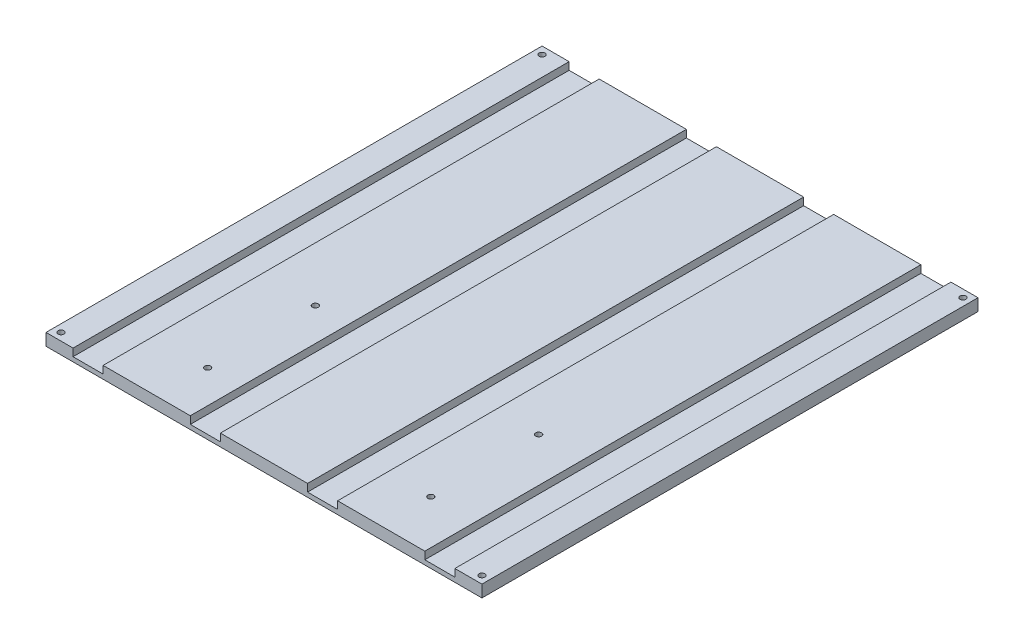
SolidWorks part; units mm, degrees
ref_plane "Front Plane" through (0, 0, 0) normal (0, 0, 1) x (1, 0, 0)
ref_plane "Top Plane" through (0, 0, 0) normal (0, 1, 0) x (1, 0, 0)
ref_plane "Right Plane" through (0, 0, 0) normal (1, 0, 0) x (0, 0, -1)
sketch "Sketch2" plane through (0, 0, 0) normal (0, 1, 0) x (1, 0, 0)
  line L0 (-24.5, -82.5) -> (-24.5, 82.5)
  line L1 (-72.5, -82.5) -> (72.5, -82.5)
  line L2 (-72.5, -82.5) -> (-72.5, 82.5)
  line L3 (-72.5, 82.5) -> (72.5, 82.5)
  line L4 (72.5, -82.5) -> (72.5, 82.5)
  line L5 (-63.5, -82.5) -> (-53.5, -82.5)
  line L6 (-63.5, -82.5) -> (-63.5, 82.5)
  line L7 (-63.5, 82.5) -> (-53.5, 82.5)
  line L8 (-53.5, -82.5) -> (-53.5, 82.5)
  line L9 (-63.5, -82.5) -> (-53.5, 82.5) construction
  line L10 (-63.5, 82.5) -> (-53.5, -82.5) construction
  line L11 (-24.5, -82.5) -> (-14.5, -82.5)
  line L12 (-14.5, -82.5) -> (-14.5, 82.5)
  line L13 (-24.5, 82.5) -> (-14.5, 82.5)
  line L14 (14.5, -82.5) -> (14.5, 82.5)
  line L15 (14.5, -82.5) -> (24.5, -82.5)
  line L16 (24.5, -82.5) -> (24.5, 82.5)
  line L17 (14.5, 82.5) -> (24.5, 82.5)
  line L18 (53.5, -82.5) -> (53.5, 82.5)
  line L19 (53.5, -82.5) -> (63.5, -82.5)
  line L20 (63.5, -82.5) -> (63.5, 82.5)
  line L21 (53.5, 82.5) -> (63.5, 82.5)
  point P0 (0, 0)
  point P6 (0, 82.5)
  point P7 (-72.5, 0)
  point P8 (-58.5, 0)
  dimension "D1" = 145
  dimension "D2" = 165
  dimension "D3" = 10
  dimension "D4" = 165
  dimension "D5" = 58.5
  dimension "D6" = 4
  dimension "D7" = 29
extrude "Boss-Extrude1" add sketch "Sketch2" against normal blind 4 contours L2 L1 L4 L3
extrude "Cut-Extrude1" cut sketch "Sketch2<3>" against normal blind 2.5 contours L6 L5 L8 L7 | L0 L13 L12 L11 | L14 L17 L16 L15 | L18 L21 L20 L19
sketch "Sketch2<3>" plane through (0, 0, 0) normal (0, 1, 0) x (1, 0, 0) same geometry as "Sketch2"
sketch "Sketch3" plane through (0, -4, 0) normal (0, -1, 0) x (1, 0, 0)
  line L0 (-70, -80) -> (70, 80)
  line L1 (-70, 80) -> (70, 80) construction
  line L2 (-70, 80) -> (-70, -80) construction
  line L3 (-70, -80) -> (70, -80) construction
  line L4 (70, 80) -> (70, -80) construction
  circle A0 centre (-70, 80) radius 0.98
  circle A1 centre (-70, 80) radius 2
  circle A2 centre (70, 80) radius 2
  circle A3 centre (70, 80) radius 0.98
  circle A4 centre (70, -80) radius 2
  circle A5 centre (70, -80) radius 0.98
  circle A6 centre (-70, -80) radius 2
  circle A7 centre (-70, -80) radius 0.98
  point P11 (0, 0)
  dimension "D1" = 1.96
  dimension "D2" = 4
  dimension "D3" = 160
  dimension "D4" = 140
extrude "Cut-Extrude3" cut sketch "Sketch3" against normal blind 5 contours A5 | A7 | A0 | A3
sketch "Sketch5" plane through (0, -4, 0) normal (0, 1, 0) x (1, 0, 0)
  line L1 (-35.4387, -29.9718) -> (38.8313, -29.9718) construction
  line L2 (-35.4387, -29.9718) -> (-35.4387, -65.8118) construction
  line L3 (-35.4387, -65.8118) -> (38.8313, -65.8118) construction
  line L4 (38.8313, -29.9718) -> (38.8313, -65.8118) construction
  circle A0 centre (-35.4387, -29.9718) radius 0.98
  circle A1 centre (38.8313, -29.9718) radius 0.98
  circle A2 centre (38.8313, -65.8118) radius 0.98
  circle A3 centre (-35.4387, -65.8118) radius 0.98
  dimension "D3" = 1.96
  dimension "D1" = 74.27
  dimension "D2" = 35.84
extrude "Cut-Extrude4" cut sketch "Sketch5" along normal blind 4 contours A0 | A1 | A2 | A3
